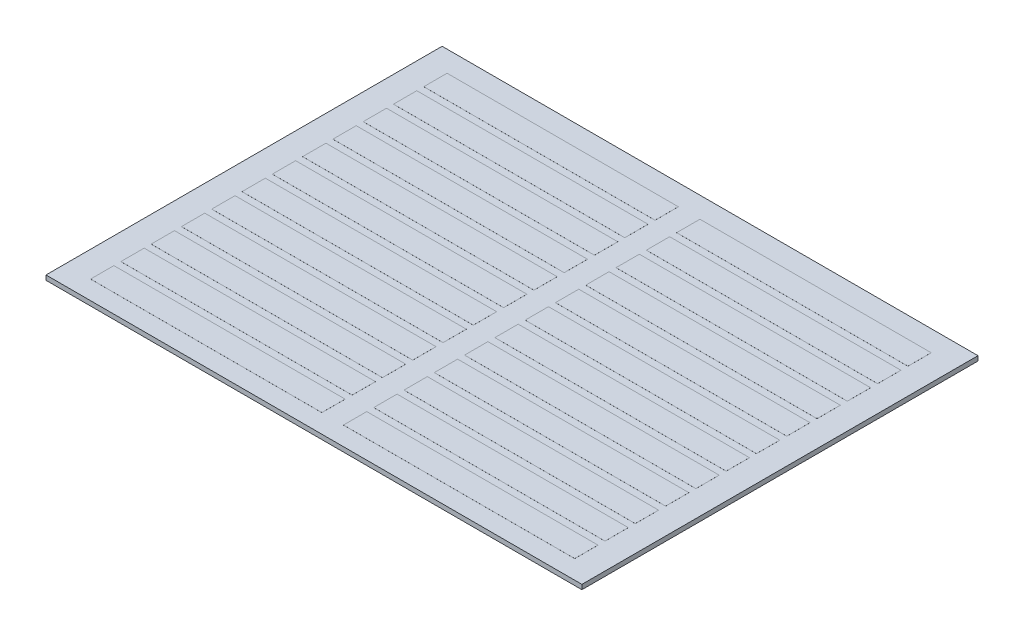
SolidWorks part; units mm, degrees
ref_plane "Спереди" through (0, 0, 0) normal (0, 0, 1) x (1, 0, 0)
ref_plane "Сверху" through (0, 0, 0) normal (0, 1, 0) x (1, 0, 0)
ref_plane "Справа" through (0, 0, 0) normal (1, 0, 0) x (0, 0, -1)
sketch "Эскиз1" plane through (0, 0, 0) normal (0, 1, 0) x (1, 0, 0)
  line L1 (-57.5, -42.5) -> (57.5, -42.5)
  line L2 (-57.5, -42.5) -> (-57.5, 42.5)
  line L3 (-57.5, 42.5) -> (57.5, 42.5)
  line L4 (57.5, -42.5) -> (57.5, 42.5)
  line L5 (-57.5, -42.5) -> (57.5, 42.5) construction
  line L6 (-57.5, 42.5) -> (57.5, -42.5) construction
  point P0 (0, 0)
  dimension "D1" = 85
  dimension "D2" = 115
extrude "Бобышка-Вытянуть1" add sketch "Эскиз1" along normal blind 1
sketch "Эскиз2" plane through (0, 1, 0) normal (0, 1, 0) x (1, 0, 0)
  line L0 (-57.5, 0) -> (57.5, 0) construction
  line L1 (2.3165, -38.4883) -> (51.945, -38.4883)
  line L2 (2.3165, -38.4883) -> (2.3165, -33.4883)
  line L3 (2.3165, -33.4883) -> (51.945, -33.4883)
  line L4 (51.945, -38.4883) -> (51.945, -33.4883)
  line L5 (2.3165, -38.4883) -> (51.945, -33.4883) construction
  line L6 (2.3165, -33.4883) -> (51.945, -38.4883) construction
  line L7 (-57.5, 42.5) -> (-57.5, -42.5) construction
  line L8 (57.5, -42.5) -> (57.5, 42.5) construction
  line L9 (0, -42.5) -> (0, 42.5) construction
  line L10 (-57.5, -42.5) -> (57.5, -42.5) construction
  line L11 (57.5, 42.5) -> (-57.5, 42.5) construction
  point P0 (27.1307, -35.9883)
  dimension "D1" = 5
extrude "Бобышка-Вытянуть2" add sketch "Эскиз2" along normal blind 0.01
pattern_linear "Линейный массив1" count 12 spacing 6.5 along (0, 0, -1) of "Бобышка-Вытянуть2"
mirror "Зеркальное отражение1" about plane through (0, 0, 0) normal (1, 0, 0) of "Линейный массив1"
